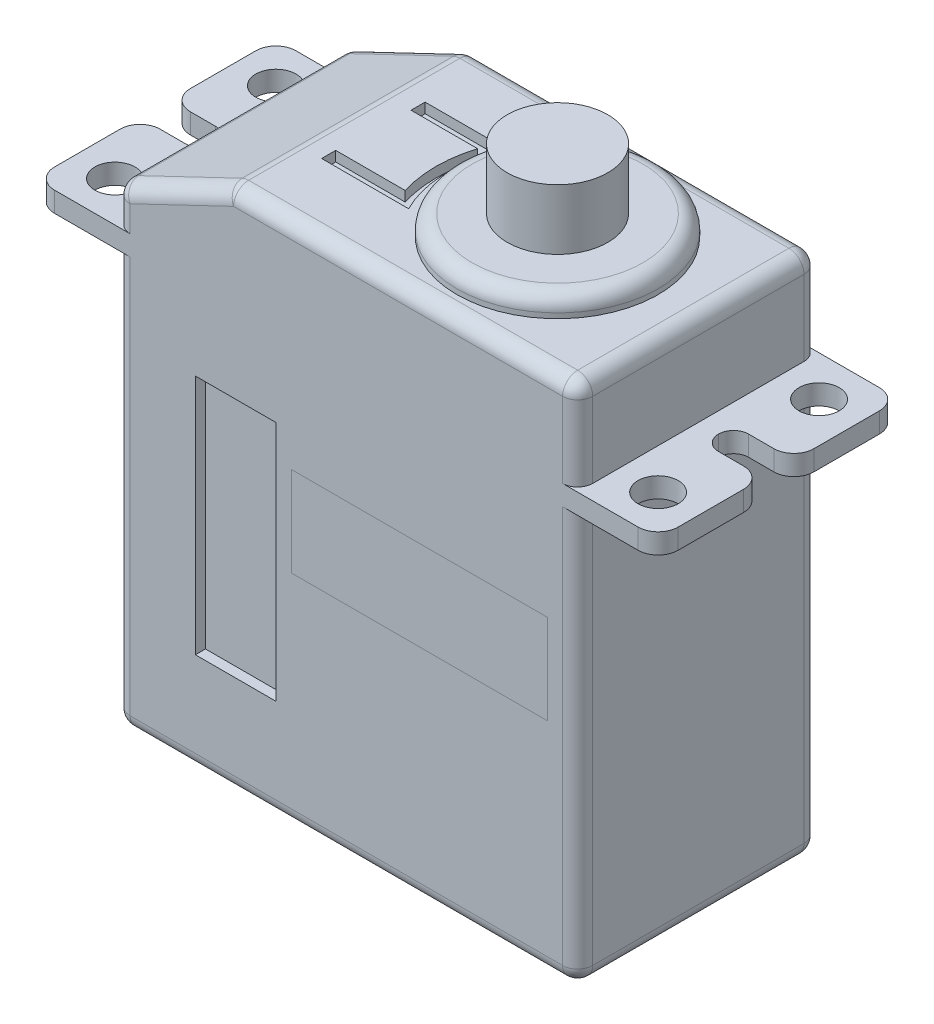
SolidWorks part; units mm, degrees
ref_plane "Front Plane" through (0, 0, 0) normal (0, 0, 1) x (1, 0, 0)
ref_plane "Top Plane" through (0, 0, 0) normal (0, 1, 0) x (1, 0, 0)
ref_plane "Right Plane" through (0, 0, 0) normal (1, 0, 0) x (0, 0, -1)
sketch "Sketch1" plane through (0, 0, 0) normal (0, 0, 1) x (1, 0, 0)
  line L1 (0, 0) -> (23, 0)
  line L2 (0, 0) -> (0, 26)
  line L3 (0, 26) -> (23, 26)
  line L4 (23, 0) -> (23, 26)
  dimension "D1" = 26
  dimension "D2" = 23
extrude "Boss-Extrude1" add sketch "Sketch1" along normal blind 12
sketch "Sketch2" plane through (0, 0, 12) normal (0, 0, 1) x (1, 0, 0)
  line L0 (5.726, 26) -> (0, 23.2609)
  line L1 (23, 26) -> (0, 26) construction
  line L2 (0, 26) -> (0, 0) construction
  line L3 (0, 23.2609) -> (0, 26)
  line L4 (0, 26) -> (5.726, 26)
extrude "Cut-Extrude1" cut sketch "Sketch2" against normal blind 12
sketch "Sketch3" plane through (0, 0, 0) normal (-1, 0, 0) x (0, 0, 1)
  line L0 (0, 23.2609) -> (0, 0) construction
  line L1 (0, 21.5) -> (12, 21.5)
  line L2 (0, 21.5) -> (0, 20.5)
  line L3 (0, 20.5) -> (12, 20.5)
  line L4 (12, 21.5) -> (12, 20.5)
  line L5 (12, 23.2609) -> (12, 0) construction
  line L6 (12, 0) -> (0, 0) construction
  dimension "D1" = 1
  dimension "D2" = 20.5
extrude "Boss-Extrude2" add sketch "Sketch3" along normal blind 4 and the other way blind 27
sketch "Sketch5" plane through (0, 21.5, 0) normal (0, 1, 0) x (1, 0, 0)
  line L0 (0, 0) -> (-4, 0) construction
  line L1 (27, 0) -> (23, 0) construction
  line L2 (0, -12) -> (-4, -12) construction
  line L3 (27, -12) -> (23, -12) construction
  circle A0 centre (-2, -10) radius 1
  circle A1 centre (-2, -2) radius 1
  circle A2 centre (25, -2) radius 1
  circle A3 centre (25, -10) radius 1
  point P10 (-2, 0)
  point P13 (25, 0)
  dimension "D5" = 2
  dimension "D1" = 2
  dimension "D2" = 2
  dimension "D3" = 2
  dimension "D4" = 2
extrude "Cut-Extrude2" cut sketch "Sketch5" against normal blind 5
sketch "Sketch6" plane through (0, 21.5, 0) normal (0, 1, 0) x (1, 0, 0)
  line L0 (-4, -12) -> (-4, 0) construction
  line L1 (-4, -5.25) -> (-1, -5.25)
  line L2 (-4, -5.25) -> (-4, -6.75)
  line L3 (-4, -6.75) -> (-1, -6.75)
  line L4 (-1, -5.25) -> (-1, -6.75)
  line L5 (27, -12) -> (27, 0) construction
  line L6 (27, -5.25) -> (24, -5.25)
  line L7 (27, -5.25) -> (27, -6.75)
  line L8 (27, -6.75) -> (24, -6.75)
  line L9 (24, -5.25) -> (24, -6.75)
  point P12 (-4, -6)
  point P13 (-1, -6)
  point P14 (27, -6)
  point P15 (24, -6)
  dimension "D1" = 1.5
  dimension "D2" = 1.5
  dimension "D3" = 3
  dimension "D4" = 3
extrude "Cut-Extrude3" cut sketch "Sketch6" against normal blind 5
fillet "Fillet1" radius 1 8 edges at (-4, 21, 5.25) (27, 21, 0) (27, 21, 5.25) (27, 21, 6.75) (27, 21, 12) (-4, 21, 12) (-4, 21, 6.75) (-4, 21, 0)
fillet "Fillet2" radius 0.75 4 edges at (-1, 21, 6.75) (-1, 21, 5.25) (24, 21, 6.75) (24, 21, 5.25)
sketch "Sketch7" plane through (0, 26, 0) normal (0, 1, 0) x (1, 0, 0)
  line L0 (23, -12) -> (23, 0) construction
  line L1 (23, -12) -> (23, 0) construction
  circle A0 centre (16, -6) radius 5
  point P4 (23, -6)
  dimension "D1" = 10
  dimension "D2" = 7
extrude "Boss-Extrude3" add sketch "Sketch7" along normal blind 1
sketch "Sketch8" plane through (0, 26, 0) normal (0, 1, 0) x (1, 0, 0)
  line L0 (11.1019, -3.5) -> (6.9174, -3.5)
  line L1 (6.9174, -3.5) -> (6.9174, -4.2)
  line L2 (6.9174, -4.2) -> (10.2291, -4.2)
  line L3 (6.7735, -8.5) -> (11.1019, -8.5)
  line L4 (6.7735, -8.5) -> (6.7735, -7.8)
  line L5 (6.7735, -7.8) -> (10.2291, -7.8)
  line L6 (23, 0) -> (5.726, 0) construction
  line L7 (23, -12) -> (5.726, -12) construction
  arc A0 (11.1019, -3.5) -> (11.1019, -8.5) centre (16, -6) ccw
  arc A1 (10.2291, -4.2) -> (10.2291, -7.8) centre (16, -6) ccw
  dimension "D1" = 0.7
  dimension "D2" = 0.7
  dimension "D3" = 3.5
  dimension "D4" = 3.5
extrude "Cut-Extrude4" cut sketch "Sketch8" against normal blind 0.5
fillet "Fillet3" radius 0.75 20 edges at (23, 0, 6) (11.5, 0, 12) (0, 0, 6) (0, 22.3805, 0) (0, 22.3805, 12) (0, 10.25, 12) (0, 10.25, 0) (11.5, 0, 0) (23, 26, 6) (23, 23.75, 12) (23, 10.25, 12) (23, 10.25, 0) (23, 23.75, 0) (16, 27, 11) (14.363, 26, 12) (2.863, 24.6305, 12) (0, 23.2609, 6) (2.863, 24.6305, 0) (5.726, 26, 6) (14.363, 26, 0)
sketch "Sketch9" plane through (0, 0, 12) normal (0, 0, 1) x (1, 0, 0)
  line L0 (22.25, 0) -> (0.75, 0) construction
  line L1 (4, 17) -> (8, 17)
  line L2 (4, 17) -> (4, 5)
  line L3 (4, 5) -> (8, 5)
  line L4 (8, 17) -> (8, 5)
  line L5 (0, 0.75) -> (0, 20.5) construction
  dimension "D1" = 12
  dimension "D2" = 4
  dimension "D3" = 5
  dimension "D4" = 4
extrude "Cut-Extrude5" cut sketch "Sketch9" against normal blind 0.5
sketch "Sketch10" plane through (0, 27, 0) normal (0, 1, 0) x (1, 0, 0)
  circle A0 centre (16, -6) radius 2.5
  dimension "D1" = 5
extrude "Boss-Extrude4" add sketch "Sketch10" along normal blind 3
sketch "Sketch11" plane through (0, 0, 12) normal (0, 0, 1) x (1, 0, 0)
  line L1 (8.7709, 15.3612) -> (21.4934, 15.3612)
  line L2 (8.7709, 15.3612) -> (8.7709, 10.9063)
  line L3 (8.7709, 10.9063) -> (21.4934, 10.9063)
  line L4 (21.4934, 15.3612) -> (21.4934, 10.9063)
split line "Split Line1"
sketch "Sketch13" plane through (0, 0, 0) normal (0, 0, -1) x (-1, 0, 0)
sketch "Sketch14" plane through (0, 0, 0) normal (0, -1, 0) x (1, 0, 0)
sketch "Sketch15" plane through (0, 26, 0) normal (0, 1, 0) x (1, 0, 0)
ref_plane "Plane1" through (6.9174, 26, 4.2) normal (1, 0, 0) x (0, 0, -1)
sketch "Sketch16" plane through (0, 0, 0) normal (0, 0, -1) x (-1, 0, 0)
  line L0 (-23, 21.5) -> (-23, 25.25) construction
  line L1 (0, 22.7883) -> (0, 21.5) construction
  line L2 (-27, 20.5) -> (-27, 21.5) construction
  line L3 (4, 21.5) -> (4, 20.5) construction
  dimension "D1" = 23
  dimension "D2" = 31
  dimension "D3" = 4
